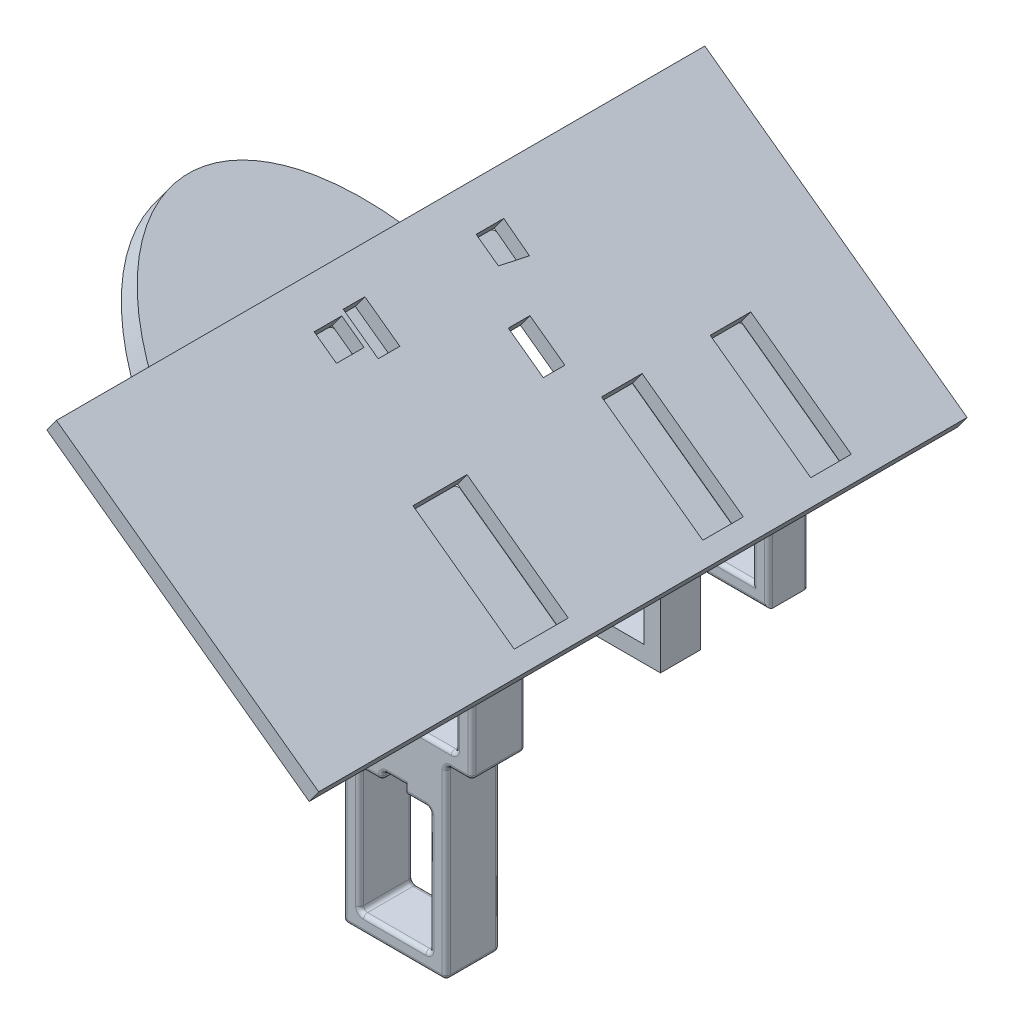
SolidWorks part; units mm, degrees
note: The reader was unsure of these and kept them because the rebuilt part matched: shared geometry of "Sketch7<2>".
ref_plane "Front Plane" through (0, 0, 0) normal (0, 0, 1) x (1, 0, 0)
ref_plane "Top Plane" through (0, 0, 0) normal (0, 1, 0) x (1, 0, 0)
ref_plane "Right Plane" through (0, 0, 0) normal (1, 0, 0) x (0, 0, -1)
sketch "Sketch3" plane through (0, 0, 0) normal (0, 0, 1) x (1, 0, 0)
  line L0 (-14.3013, 7.2013) -> (14.3013, 7.2013) construction
  line L1 (-11.25, -4.15) -> (11.25, -4.15)
  line L2 (-11.25, -4.15) -> (-11.25, 4.15)
  line L3 (-11.25, 4.15) -> (11.25, 4.15)
  line L4 (11.25, -4.15) -> (11.25, 4.15)
  line L5 (-11.25, -4.15) -> (11.25, 4.15) construction
  line L6 (-11.25, 4.15) -> (11.25, -4.15) construction
  line L7 (-6.5, -15.45) -> (6.5, -15.45) construction
  line L8 (-6.5, -15.45) -> (-6.5, -38.55)
  line L9 (-6.5, -38.55) -> (6.5, -38.55)
  line L10 (6.5, -15.45) -> (6.5, -38.55)
  line L11 (-6.5, -15.45) -> (6.5, -38.55) construction
  line L12 (-6.5, -38.55) -> (6.5, -15.45) construction
  line L13 (14.3013, -7.2013) -> (14.3013, 7.2013)
  line L15 (-14.3013, -7.2013) -> (-14.3013, 7.2013)
  line L16 (9.5513, -12.3987) -> (9.5513, -41.6013)
  line L17 (-9.5513, -41.6013) -> (9.5513, -41.6013)
  line L18 (-9.5513, -12.3987) -> (-9.5513, -41.6013)
  line L20 (-9.5513, -12.3987) -> (9.5513, -12.3987) construction
  line L21 (-14.3013, -7.2013) -> (14.3013, -7.2013) construction
  line L22 (-9.5513, -12.3987) -> (-9.5513, -7.2013)
  line L23 (-9.5513, -7.2013) -> (-14.3013, -7.2013)
  line L24 (14.3013, -7.2013) -> (9.5513, -7.2013)
  line L25 (9.5513, -7.2013) -> (9.5513, -12.3987)
  line L26 (-14.3013, 7.2013) -> (1.6877, 29.2083)
  line L27 (1.6877, 29.2083) -> (20.4084, 15.607)
  line L28 (20.4084, 15.607) -> (14.3013, 7.2013)
  line L29 (0, -41.6013) -> (0, 7.2013) construction
  line L30 (-6.5, -15.45) -> (-2.25, -15.45)
  line L31 (-2.25, -15.45) -> (-2.25, -13.95)
  line L32 (-2.25, -13.95) -> (2.25, -13.95)
  line L33 (2.25, -13.95) -> (2.25, -15.45)
  line L34 (2.25, -15.45) -> (6.5, -15.45)
  point P0 (0, 0)
  point P5 (0, -27)
  point P28 (0, -13.95)
  dimension "D1" = 22.5
  dimension "D2" = 8.3
  dimension "D3" = 27
  dimension "D4" = 13
  dimension "D5" = 23.1
  dimension "D7" = 3.0513
  dimension "D8" = 54
  dimension "D9" = 10.39
  dimension "D11" = 19.1026
  dimension "D12" = 4.5
  dimension "D13" = 1.5
  dimension "D6" = 23.14
extrude "Boss-Extrude1" add sketch "Sketch3" along normal blind 9.9
sketch "Sketch4" plane through (14.4725, 19.9197, 0) normal (0.5878, 0.809, 0) x (0.809, -0.5878, 0)
  line L0 (-4.2328, 0) -> (-4.2328, -9.9) construction
  line L1 (7.3372, 0) -> (-15.8028, 0) construction
  line L2 (7.3372, -9.9) -> (-15.8028, -9.9) construction
  line L3 (-15.8028, -4.95) -> (7.3372, -4.95) construction
  line L4 (-15.8028, -9.9) -> (-15.8028, 0) construction
  line L5 (7.3372, -9.9) -> (7.3372, 0) construction
  line L7 (-49.2328, 71.1) -> (10.7672, 71.1)
  line L8 (-49.2328, 71.1) -> (-49.2328, -48.9)
  line L9 (-49.2328, -48.9) -> (10.7672, -48.9)
  line L10 (10.7672, 71.1) -> (10.7672, -48.9)
  line L11 (-49.2328, 71.1) -> (10.7672, -48.9) construction
  line L12 (-49.2328, -48.9) -> (10.7672, 71.1) construction
  point P12 (-4.2328, -4.95)
  point P13 (-19.2328, 11.1)
  dimension "D1" = 120
  dimension "D2" = 60
  dimension "D3" = 16.05
  dimension "D4" = 15
extrude "Boss-Extrude2" add sketch "Sketch4" along normal blind 3
sketch "Sketch7" plane through (14.4725, 19.9197, 0) normal (-0.5878, -0.809, 0) x (0.809, -0.5878, 0)
  line L0 (-15.8298, -11.1) -> (-64.8298, -11.1) construction
  line L1 (-49.2328, 48.9) -> (10.7672, 48.9) construction
  line L6 (-37.2199, 1.6898) -> (-42.3199, 1.6898)
  line L7 (-37.2199, 1.6898) -> (-37.2199, 6.7898)
  line L8 (-37.2199, 6.7898) -> (-42.3199, 6.7898)
  line L9 (-42.3199, 1.6898) -> (-42.3199, 6.7898)
  line L10 (-37.2199, 1.6898) -> (-42.3199, 6.7898) construction
  line L11 (-37.2199, 6.7898) -> (-42.3199, 1.6898) construction
  line L12 (-49.2328, -71.1) -> (-49.2328, 48.9) construction
  line L13 (-37.6687, -23.55) -> (-36.7711, -28.5704)
  line L14 (-37.6687, -23.55) -> (-42.7687, -23.55)
  line L15 (-42.7687, -23.55) -> (-42.7687, -28.65)
  line L16 (-36.7711, -28.5704) -> (-42.7687, -28.65)
  line L17 (-42.7687, -23.55) -> (-36.7711, -28.5704) construction
  point P4 (-40.2187, 3.9)
  point P10 (-39.7699, -26.0602)
  point P11 (-39.7699, 4.2398)
  dimension "D1" = 15
  dimension "D2" = 9.0141
  dimension "D3" = 5.1
  dimension "D4" = 5.1
  dimension "D5" = 5.1
  dimension "D6" = 6.4641
  dimension "D7" = 12.45
  dimension "D8" = 60
  dimension "D9" = 30.3
extrude "Boss-Extrude3" add sketch "Sketch7" along normal blind 24.5 and the other way blind 3
sketch "Sketch8" plane through (0.0718, 0.0988, 0) normal (-0.5878, -0.809, 0) x (0.809, -0.5878, 0)
  line L2 (-24.2187, 5.8504) -> (-24.2187, -28.0504)
  line L3 (-24.2187, 5.8504) -> (-35.5324, 17.1641)
  line L4 (-24.2187, -28.0504) -> (-35.5324, -39.3641)
  line L6 (10.7672, -71.1) -> (-49.2328, -71.1) construction
  line L7 (-49.2328, 48.9) -> (10.7672, -71.1) construction
  line L8 (-19.2328, -11.1) -> (-49.2328, -11.1) construction
  line L9 (10.7672, 48.9) -> (10.7672, -71.1) construction
  ellipse E0 centre (-24.2187, -11.1) end of major axis (-73.1897, -11.1) minor radius 29.05 (-35.5324, 17.1641) -> (-35.5324, -39.3641) ccw
  dimension "D1" = 4.9859
  dimension "D2" = 28.2641
  dimension "D3" = 23.9569
  dimension "D4" = 45
  dimension "D5" = 16
  dimension "D6" = 48.9709
  dimension "D7" = 60
  dimension "D8" = 34.9859
extrude "Boss-Extrude4" add sketch "Sketch8" along normal blind 5
ref_plane "Plane1" through (0, 0, -25) normal (0, 0, -1) x (-1, 0, 0)
ref_plane "Plane2" through (0, 0, -45) normal (0, 0, -1) x (-1, 0, 0)
sketch "Sketch9" plane through (0, 0, -25) normal (0, 0, -1) x (-1, 0, 0)
  line L0 (-22.1718, 18.034) -> (-14.3013, 7.2013)
  line L2 (-3.4511, 31.6354) -> (14.3013, 7.2013)
  line L3 (14.3013, 7.2013) -> (14.3013, -7.2013)
  line L4 (14.3013, -7.2013) -> (9.5513, -7.2013)
  line L5 (9.5513, -7.2013) -> (-14.3013, -7.2013)
  line L6 (-14.3013, -7.2013) -> (-14.3013, 7.2013)
  line L7 (-11.25, 4.15) -> (11.25, 4.15)
  line L8 (11.25, 4.15) -> (11.25, -4.15)
  line L9 (11.25, -4.15) -> (-11.25, -4.15)
  line L10 (-11.25, -4.15) -> (-11.25, 4.15)
  line L12 (-24.9467, 16.0179) -> (-23.1833, 13.5909) construction
  line L13 (-24.9467, 16.0179) -> (23.5943, 51.2851) construction
  line L14 (-22.1718, 18.034) -> (-3.4511, 31.6354)
  dimension "D1" = 3.43
extrude "Boss-Extrude5" add sketch "Sketch9" along normal blind 7.4 contours L10 L9 L8 L7 | L0 L6 L5 L4 L3 L2 L14
sketch "Sketch10" plane through (0, 0, -45) normal (0, 0, -1) x (-1, 0, 0)
  line L0 (-22.1718, 18.034) -> (-14.3013, 7.2013)
  line L1 (-22.1718, 18.034) -> (-3.4511, 31.6354)
  line L2 (-3.4511, 31.6354) -> (14.3013, 7.2013)
  line L3 (14.3013, 7.2013) -> (14.3013, -7.2013)
  line L6 (-14.3013, -7.2013) -> (-14.3013, 7.2013)
  line L7 (-11.25, 4.15) -> (11.25, 4.15)
  line L8 (11.25, 4.15) -> (11.25, -4.15)
  line L9 (11.25, -4.15) -> (-11.25, -4.15)
  line L10 (-11.25, -4.15) -> (-11.25, 4.15)
  line L11 (-24.9467, 16.0179) -> (23.5943, 51.2851) construction
  line L13 (-20.4084, 15.607) -> (-14.3013, 7.2013) construction
  line L14 (-14.3013, -7.2013) -> (-14.3013, 7.2013) construction
  line L16 (-1.6877, 29.2083) -> (14.3013, 7.2013) construction
  line L17 (14.3013, 7.2013) -> (14.3013, -7.2013) construction
  line L18 (-14.3013, -7.2013) -> (14.3013, -7.2013)
extrude "Boss-Extrude6" add sketch "Sketch10" along normal blind 7.4
sketch "Sketch11" plane through (14.4725, 19.9197, 0) normal (-0.5878, -0.809, 0) x (0.809, -0.5878, 0)
  line L0 (-15.8028, 9.9) -> (-15.8028, 0) construction
  line L9 (7.3372, 9.9) -> (7.3372, 0) construction
  line L10 (-49.2328, 48.9) -> (10.7672, 48.9) construction
  line L11 (-15.8028, -32.4) -> (-15.8028, -25) construction
  line L12 (10.7672, 48.9) -> (10.7672, -71.1) construction
  line L13 (7.3372, 9.9) -> (-15.8028, 9.9) construction
  line L24 (-15.8128, 9.95) -> (7.3472, 9.95)
  line L25 (-15.8128, 9.95) -> (-15.8128, -0.05)
  line L26 (-15.8128, -0.05) -> (7.3472, -0.05)
  line L27 (7.3472, 9.95) -> (7.3472, -0.05)
  line L28 (-37.611, 48.9) -> (-37.611, -71.1) construction
  line L29 (7.3372, 0) -> (-15.8028, 0) construction
  line L30 (-15.8113, -24.95) -> (7.3457, -24.95)
  line L35 (-15.8113, -24.95) -> (-15.8113, -32.45)
  line L36 (-15.8113, -32.45) -> (7.3457, -32.45)
  line L37 (7.3457, -24.95) -> (7.3457, -32.45)
  line L38 (-15.8028, -32.4) -> (7.3372, -32.4) construction
  line L39 (7.3372, -32.4) -> (7.3372, -25) construction
  line L40 (-15.8028, -25) -> (7.3372, -25) construction
  line L42 (-15.6828, -44.95) -> (7.3172, -44.95)
  line L43 (-15.6828, -44.95) -> (-15.6828, -52.45)
  line L44 (-15.6828, -52.45) -> (7.3172, -52.45)
  line L45 (7.3172, -44.95) -> (7.3172, -52.45)
  line L46 (10.7672, -71.1) -> (-49.2328, -71.1) construction
  line L47 (-15.8028, -45) -> (-15.8028, -52.4) construction
  line L48 (-15.8028, -52.4) -> (7.3372, -52.4) construction
  point P20 (-37.611, -11.1)
  dimension "D2" = 38.95
  dimension "D3" = 3.42
  dimension "D4" = 23.16
  dimension "D5" = 23.157
  dimension "D6" = 7.5
  dimension "D7" = 3.45
  dimension "D8" = 23
  dimension "D9" = 3.4215
  dimension "D10" = 7.5
  dimension "D11" = 73.85
  dimension "D12" = 18.65
  dimension "D13" = 10
  dimension "D14" = 0.01
  dimension "D15" = 0.01
  dimension "D16" = 0.05
  dimension "D17" = 0.05
  dimension "D18" = 0.0085
  dimension "D19" = 0.05
  dimension "D20" = 0.0085
  dimension "D21" = 0.05
  dimension "D22" = 0.12
  dimension "D23" = 0.05
  dimension "D24" = 13.85
  dimension "D25" = 33.85
extrude "Cut-Extrude4" cut sketch "Sketch7<2>" against normal blind 10
sketch "Sketch7<2>" plane through (14.4725, 19.9197, 0) normal (-0.5878, -0.809, 0) x (0.809, -0.5878, 0) same geometry as "Sketch7"
sketch "Sketch6" plane through (14.4725, 19.9197, 0) normal (-0.5878, -0.809, 0) x (0.809, -0.5878, 0)
  line L1 (-21.8828, -23.075) -> (-29.8828, -23.075)
  line L2 (-21.8828, -23.075) -> (-21.8828, -19.075)
  line L3 (-21.8828, -19.075) -> (-29.8828, -19.075)
  line L4 (-29.8828, -23.075) -> (-29.8828, -19.075)
  line L5 (-34.9828, -3.125) -> (-42.9828, -3.125)
  line L6 (-34.9828, -3.125) -> (-34.9828, 0.875)
  line L7 (-34.9828, 0.875) -> (-42.9828, 0.875)
  line L10 (-49.2328, -71.1) -> (-49.2328, 48.9) construction
  line L11 (-42.9828, 0.875) -> (-42.9828, -3.125)
  line L12 (-49.2328, 48.9) -> (10.7672, 48.9) construction
  dimension "D1" = 8
  dimension "D2" = 6.25
  dimension "D3" = 4
  dimension "D4" = 48.025
  dimension "D5" = 15.95
  dimension "D6" = 19.35
  dimension "D7" = 8
  dimension "D8" = 4
extrude "Cut-Extrude1" cut sketch "Sketch6" against normal up to surface (3 mm away) up to face at (-15.9387, 45.7229, 4.2398)
fillet "Fillet1" radius 0.75 56 edges at (-11.25, 0, 9.9) (-11.25, 0, 0) (-11.9263, -7.2013, 9.9) (-11.9263, -7.2013, 0) (11.9263, -7.2013, 9.9) (11.9263, -7.2013, 0) (0, -38.55, 9.9) (0, -38.55, 0) (-6.5, -38.55, 4.95) (-6.5, -27, 9.9) (-6.5, -27, 0) (6.5, -27, 9.9) (6.5, -38.55, 4.95) (6.5, -27, 0) (0, -41.6013, 9.9) (0, -41.6013, 0) (9.5513, -41.6013, 4.95) (9.5513, -24.4013, 9.9) (9.5513, -7.2013, 4.95) (9.5513, -24.4013, 0) (14.3013, -7.2013, 4.95) (14.3013, 0, 9.9) (14.3013, 7.2013, 4.95) (14.3013, 0, 0) (-9.5513, -7.2013, 4.95) (-9.5513, -24.4013, 9.9) (-9.5513, -41.6013, 4.95) (-9.5513, -24.4013, 0) (-14.3013, 7.2013, 4.95) (-14.3013, 0, 9.9) (-14.3013, -7.2013, 4.95) (-14.3013, 0, 0) (11.25, 0, 9.9) (11.25, 0, 0) (-11.25, 4.15, 4.95) (0, 4.15, 9.9) (11.25, 4.15, 4.95) (0, 4.15, 0) (11.25, -4.15, 4.95) (0, -4.15, 9.9) (-11.25, -4.15, 4.95) (0, -4.15, 0) (17.3549, 11.4041, 9.9) (17.3549, 11.4041, 0) (-6.3068, 18.2048, 9.9) (-6.3068, 18.2048, 0) (-4.375, -15.45, 9.9) (-4.375, -15.45, 0) (4.375, -15.45, 9.9) (4.375, -15.45, 0) (-6.5, -15.45, 4.95) (6.5, -15.45, 4.95) (0, -13.95, 0) (-2.25, -15.45, 4.95) (-2.25, -13.95, 4.95) (0, -13.95, 9.9)
fillet "Fillet4" radius 0.75 24 edges at (14.3013, 7.2013, -48.7) (-14.3013, 7.2013, -48.7) (17.3549, 11.4041, -45) (14.3013, 0, -45) (-14.3013, 0, -45) (-6.3068, 18.2048, -45) (-11.25, 0, -45) (0, -4.15, -45) (11.25, 0, -45) (0, 4.15, -45) (-14.3013, 0, -52.4) (14.3013, 0, -52.4) (17.3549, 11.4041, -52.4) (-6.3068, 18.2048, -52.4) (0, -4.15, -52.4) (-11.25, 0, -52.4) (0, 4.15, -52.4) (11.25, 0, -52.4) (-11.25, -4.15, -48.7) (11.25, 4.15, -48.7) (-11.25, 4.15, -48.7) (-14.3013, -7.2013, -48.7) (0, -7.2013, -45) (0, -7.2013, -52.4)
chamfer "Chamfer1" distance 2 angle 45 8 edges at (-32.1028, 23.4749, 1.6898) (-30.0398, 21.9761, 4.2398) (-32.1028, 23.4749, 6.7898) (-34.1658, 24.9738, 4.2398) (-32.4659, 23.7387, -23.55) (-30.0398, 21.9761, -26.0602) (-32.1028, 23.4749, -28.6102) (-34.5289, 25.2376, -26.1)
fillet "Fillet6" radius 0.75 8 edges at (-22.2516, 32.6956, 1.6898) (-22.2516, 32.6956, 6.7898) (-26.3776, 35.6933, 1.6898) (-26.3776, 35.6933, 6.7898) (-22.6147, 32.9594, -23.55) (-26.7407, 35.9571, -23.55) (-21.8886, 32.4318, -28.5704) (-26.7407, 35.9571, -28.65)
extrude "Cut-Extrude5" cut sketch "Sketch11" against normal blind 10
